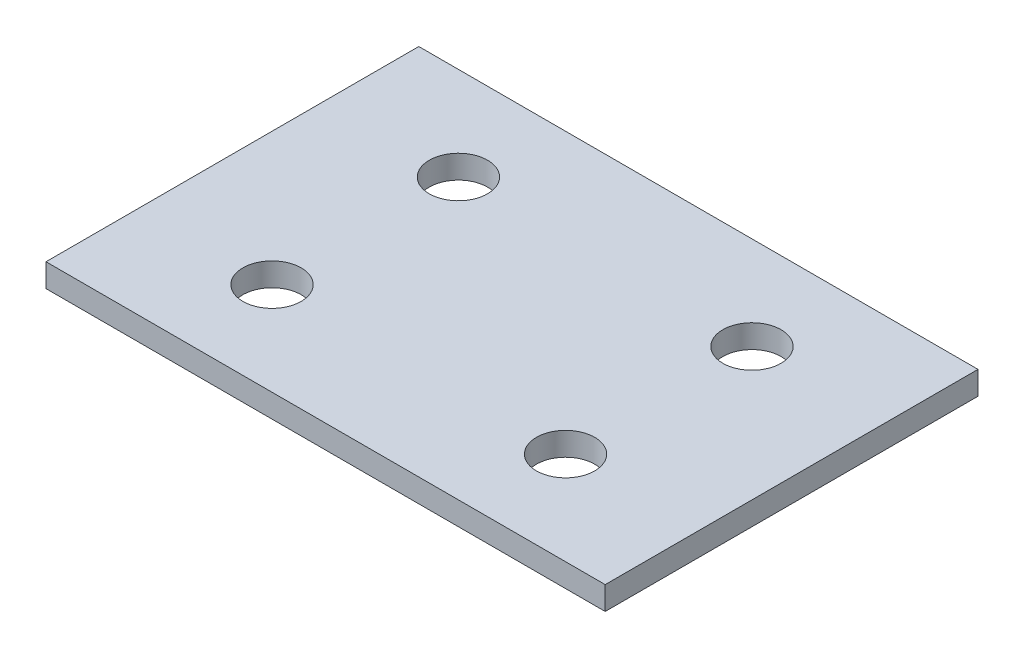
SolidWorks part; units mm, degrees
ref_plane "Front Plane" through (0, 0, 0) normal (0, 0, 1) x (1, 0, 0)
ref_plane "Top Plane" through (0, 0, 0) normal (0, 1, 0) x (1, 0, 0)
ref_plane "Right Plane" through (0, 0, 0) normal (1, 0, 0) x (0, 0, -1)
sketch "Sketch1" plane through (0, 0, 0) normal (0, 1, 0) x (1, 0, 0)
  line L1 (0, 0) -> (76.2, 0)
  line L2 (0, 0) -> (0, 50.8)
  line L3 (0, 50.8) -> (76.2, 50.8)
  line L4 (76.2, 0) -> (76.2, 50.8)
  dimension "D1" = 76.2
  dimension "D2" = 50.8
extrude "Boss-Extrude1" add sketch "Sketch1" along normal blind 3.175
sketch "Sketch3" plane through (0, 3.175, 0) normal (0, 1, 0) x (1, 0, 0)
  line L0 (18.1, 50.8) -> (18.1, 0) construction
  line L1 (76.2, 50.8) -> (0, 50.8) construction
  line L2 (0, 0) -> (76.2, 0) construction
  line L3 (58.1, 50.8) -> (58.1, 0) construction
  line L4 (18.1, 25.4) -> (58.1, 25.4) construction
  circle A0 centre (18.1, 38.1) radius 3.9688
  circle A1 centre (18.1, 12.7) radius 3.9688
  circle A2 centre (58.1, 38.1) radius 3.9687
  circle A3 centre (58.1, 12.7) radius 3.9687
  point P18 (38.1, 25.4)
  point P19 (38.1, 50.8)
  dimension "D5" = 7.9375
  dimension "D1" = 40
  dimension "D3" = 25.4
  dimension "D4" = 12.7
extrude "Cut-Extrude1" cut sketch "Sketch3" against normal through all
